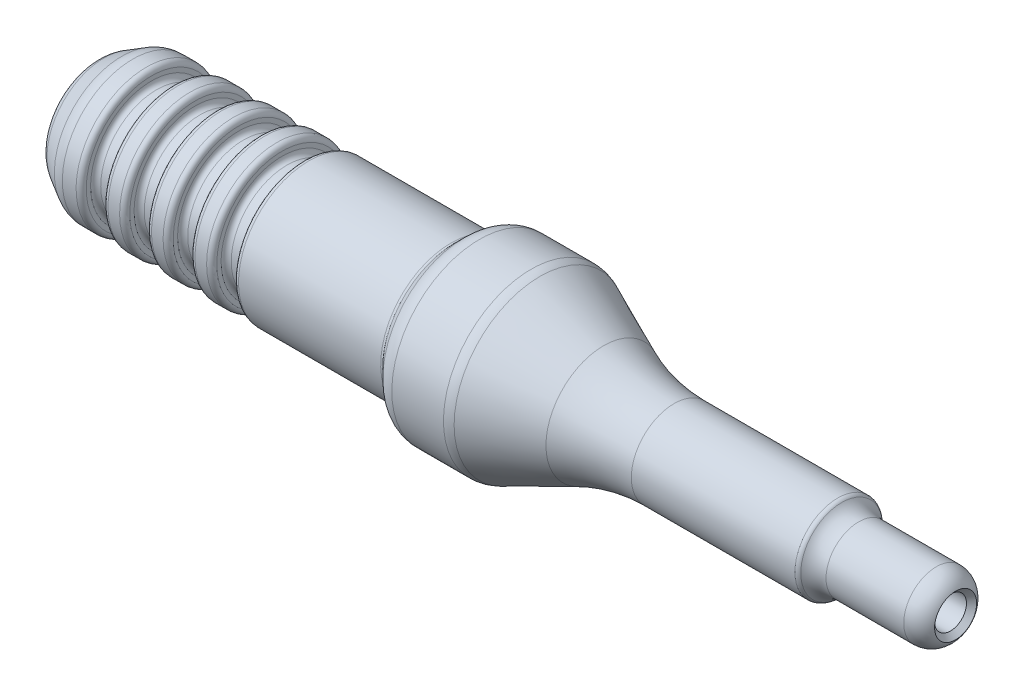
SolidWorks part; units mm, degrees
ref_plane "Front Plane" through (0, 0, 0) normal (0, 0, 1) x (1, 0, 0)
ref_plane "Top Plane" through (0, 0, 0) normal (0, 1, 0) x (1, 0, 0)
ref_plane "Right Plane" through (0, 0, 0) normal (1, 0, 0) x (0, 0, -1)
sketch "Sketch1" plane through (0, 0, 0) normal (0, 0, 1) x (1, 0, 0)
  line L0 (0, 0) -> (0, 3.52)
  line L1 (0, 3.52) -> (2.3, 4.8479)
  line L2 (2.3, 4.8479) -> (24.8, 4.8479)
  line L3 (24.8, 4.8479) -> (26, 6.0479)
  line L4 (26, 6.0479) -> (30.5, 6.0479)
  line L5 (30.5, 6.0479) -> (37.5, 2.9474)
  line L6 (37.5, 2.9474) -> (51.5, 2.9474)
  line L7 (51.5, 2.9474) -> (51.9026, 2.25)
  line L8 (51.9026, 2.25) -> (59.4526, 2.25)
  line L9 (59.4526, 2.25) -> (59.4526, 0)
  line L10 (59.4526, 0) -> (0, 0)
  dimension "D1" = 3.52
  dimension "D2" = 2.3
  dimension "D3" = 22.5
  dimension "D4" = 30
  dimension "D5" = 45
  dimension "D6" = 1.2
  dimension "D7" = 4.5
  dimension "D8" = 7
  dimension "D9" = 156.11
  dimension "D10" = 14
  dimension "D11" = 120
  dimension "D12" = 7.55
  dimension "D13" = 2.25
revolve "Revolve1" add sketch "Sketch1" angle 360 about L10
sketch "Sketch2" plane through (0, 0, 0) normal (0, 0, 1) x (1, 0, 0)
  line L0 (0, 2.25) -> (33.5, 2.25)
  line L1 (0, 3.52) -> (0, -3.52) construction
  line L2 (33.5, 2.25) -> (35.4919, 1.1)
  line L3 (35.4919, 1.1) -> (59.4526, 1.1)
  line L4 (59.4526, -2.25) -> (59.4526, 2.25) construction
  line L5 (59.4526, 1.1) -> (59.4526, 0)
  line L6 (59.4526, 0) -> (0, 0)
  line L7 (0, 0) -> (0, 2.25)
  dimension "D1" = 2.25
  dimension "D2" = 150
  dimension "D3" = 33.5
  dimension "D4" = 1.1
sketch "Sketch3" plane through (0, 0, 0) normal (0, 0, 1) x (1, 0, 0)
  line L0 (2.3, 4.8479) -> (24.8, 4.8479) construction
  line L1 (4, 4.8479) -> (5.5, 4.8479)
  line L2 (4, 4.8479) -> (4, 3.8479)
  line L3 (4, 3.8479) -> (5.5, 3.8479)
  line L4 (5.5, 4.8479) -> (5.5, 3.8479)
  line L6 (59.4526, 0) -> (0, 0) construction
  line L7 (7, 4.8479) -> (7, 3.8479)
  line L8 (7, 4.8479) -> (8.5, 4.8479)
  line L9 (8.5, 4.8479) -> (8.5, 3.8479)
  line L10 (7, 3.8479) -> (8.5, 3.8479)
  line L11 (10, 4.8479) -> (10, 3.8479)
  line L12 (10, 4.8479) -> (11.5, 4.8479)
  line L13 (11.5, 4.8479) -> (11.5, 3.8479)
  line L14 (10, 3.8479) -> (11.5, 3.8479)
  line L15 (13, 4.8479) -> (13, 3.8479)
  line L16 (13, 4.8479) -> (14.5, 4.8479)
  line L17 (14.5, 4.8479) -> (14.5, 3.8479)
  line L18 (13, 3.8479) -> (14.5, 3.8479)
  dimension "D1" = 1.5
  dimension "D2" = 1
  dimension "D3" = 4
  dimension "D4" = 4.8479
  dimension "D5" = 4
revolve "Cut-Revolve1" cut sketch "Sketch2" angle 360 about L10
revolve "Cut-Revolve2" cut sketch "Sketch3" angle 360 about L10
fillet "Fillet1" radius 12 1 edges at (37.5, 2.9474, 0)
chamfer "Chamfer1" distance 0.35 angle 45 2 edges at (59.4526, 1.1, 0) (0, 2.25, 0)
fillet "Fillet2" radius 1.5 6 edges at (51.9026, 2.25, 0) (2.3, 4.8479, 0) (0, 3.52, 0) (26, 6.0479, 0) (30.5, 6.0479, 0) (59.4526, 2.25, 0)
fillet "Fillet3" radius 0.35 15 edges at (4, 3.8479, 0) (13, 3.8479, 0) (14.5, 3.8479, 0) (13, 4.8479, 0) (11.5, 4.8479, 0) (10, 3.8479, 0) (11.5, 3.8479, 0) (10, 4.8479, 0) (8.5, 4.8479, 0) (7, 3.8479, 0) (8.5, 3.8479, 0) (7, 4.8479, 0) (5.5, 4.8479, 0) (14.5, 4.8479, 0) (4, 4.8479, 0)
fillet "Fillet4" radius 0.35 2 edges at (51.5, 2.9474, 0) (24.8, 4.8479, 0)
